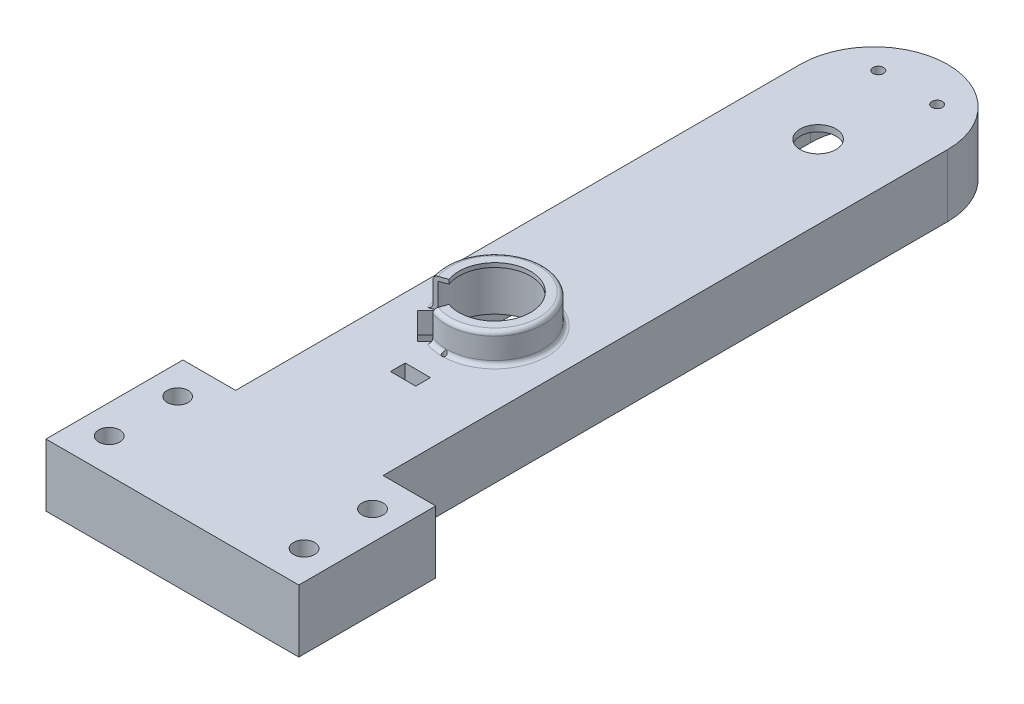
SolidWorks part; units mm, degrees
ref_plane "Front Plane" through (0, 0, 0) normal (0, 0, 1) x (1, 0, 0)
ref_plane "Top Plane" through (0, 0, 0) normal (0, 1, 0) x (1, 0, 0)
ref_plane "Right Plane" through (0, 0, 0) normal (1, 0, 0) x (0, 0, -1)
sketch "Sketch1" plane through (0, 0, 0) normal (0, 1, 0) x (1, 0, 0)
  line L0 (-5.6852, 33.5) -> (5.6852, 33.5)
  line L1 (0, 0) -> (0, 26.5) construction
  line L2 (0, 26.5) -> (0, 33.5) construction
  line L3 (-5.6852, 33.5) -> (-11.4774, 17.5861)
  line L4 (0, 0) -> (-21, 0) construction
  line L5 (5.6852, 33.5) -> (11.4774, 17.5861)
  line L6 (5.6852, -33.5) -> (11.4774, -17.5861)
  line L7 (-5.6852, -33.5) -> (5.6852, -33.5)
  line L8 (-5.6852, -33.5) -> (-11.4774, -17.5861)
  line L9 (0, 0) -> (0, -243.5) construction
  line L11 (-30, 26.5) -> (-30, -243.5)
  line L12 (-30, -243.5) -> (30, -243.5)
  line L13 (30, 26.5) -> (30, -243.5)
  arc A0 (-11.4774, 17.5861) -> (-11.4774, -17.5861) centre (0, 0) ccw
  circle A1 centre (0, 26.5) radius 3.5
  circle A2 centre (0, -26.5) radius 3.5
  arc A3 (11.4774, -17.5861) -> (11.4774, 17.5861) centre (0, 0) ccw
  arc A5 (30, 26.5) -> (-30, 26.5) centre (0, 26.5) ccw
  point P1 (0, 56.5)
  dimension "D1" = 11.3704
  dimension "D2" = 42
  dimension "D4" = 7
  dimension "D6" = 7
  dimension "D3" = 33.5
  dimension "D5" = 110
  dimension "D7" = 300
  dimension "D8" = 30
extrude "Boss-Extrude1" add sketch "Sketch1" along normal blind 10 contours L13 A5 L11 L12 A3 L6 L7 L8 A0 L3 L0 L5 region at (0, 0, 107.816)
sketch "Sketch2" plane through (0, 10, 0) normal (0, 1, 0) x (1, 0, 0)
  line L0 (5.6852, 33.5) -> (11.4774, 17.5861) construction
  line L1 (5.6852, -33.5) -> (11.4774, -17.5861) construction
  line L2 (-5.6852, -33.5) -> (5.6852, -33.5) construction
  line L3 (-5.6852, -33.5) -> (-11.4774, -17.5861) construction
  line L4 (-5.6852, 33.5) -> (-11.4774, 17.5861) construction
  line L5 (-5.6852, 33.5) -> (5.6852, 33.5) construction
  line L6 (5.6852, 33.5) -> (11.4774, 17.5861)
  line L7 (5.6852, -33.5) -> (11.4774, -17.5861)
  line L8 (-5.6852, -33.5) -> (5.6852, -33.5)
  line L9 (-5.6852, -33.5) -> (-11.4774, -17.5861)
  line L10 (-5.6852, 33.5) -> (-11.4774, 17.5861)
  line L11 (-5.6852, 33.5) -> (5.6852, 33.5)
  line L12 (-21, 0) -> (0, 0) construction
  arc A0 (11.4774, -17.5861) -> (11.4774, 17.5861) centre (0, 0) ccw construction
  arc A1 (-11.4774, 17.5861) -> (-11.4774, -17.5861) centre (0, 0) ccw construction
  arc A2 (11.4774, -17.5861) -> (11.4774, 17.5861) centre (0, 0) ccw
  arc A3 (-11.4774, 17.5861) -> (-11.4774, -17.5861) centre (0, 0) ccw
  circle A4 centre (0, 26.5) radius 3.5
  circle A5 centre (0, -26.5) radius 3.5
  circle A6 centre (0, 0) radius 7.5
  dimension "D2" = 7
  dimension "D1" = 7
extrude "Boss-Extrude2" add sketch "Sketch2" against normal blind 3
sketch "Sketch5" plane through (0, 7, 0) normal (0, -1, 0) x (1, 0, 0)
  line L0 (11.4774, -17.5861) -> (5.6852, -33.5) construction
  line L1 (-5.6852, -33.5) -> (5.6852, -33.5) construction
  line L2 (-5.6852, -33.5) -> (-11.4774, -17.5861) construction
  line L3 (5.6852, 33.5) -> (11.4774, 17.5861) construction
  line L4 (-5.6852, 33.5) -> (5.6852, 33.5) construction
  line L5 (-5.6852, 33.5) -> (-11.4774, 17.5861) construction
  line L6 (11.4774, -17.5861) -> (5.6852, -33.5)
  line L7 (-5.6852, -33.5) -> (5.6852, -33.5)
  line L8 (-5.6852, -33.5) -> (-11.4774, -17.5861)
  line L9 (5.6852, 33.5) -> (11.4774, 17.5861)
  line L10 (-5.6852, 33.5) -> (5.6852, 33.5)
  line L11 (-5.6852, 33.5) -> (-11.4774, 17.5861)
  arc A4 (-11.4774, -17.5861) -> (11.4774, -17.5861) centre (0, 0) ccw
  arc A5 (11.4774, 17.5861) -> (-11.4774, 17.5861) centre (0, 0) ccw
extrude "Boss-Extrude5" add sketch "Sketch5" along normal up to surface (7 mm away) and the other way through all up to face at (0, 0, 0)
sketch "Sketch6" plane through (0, 7, 0) normal (0, -1, 0) x (1, 0, 0)
  circle A0 centre (0, 0) radius 8.5
extrude "Cut-Extrude1" cut sketch "Sketch6" against normal through all
sketch "Sketch7" plane through (0, 0, 0) normal (0, -1, 0) x (1, 0, 0)
  line L0 (0, 243.5) -> (0, 153.5) construction
  line L1 (-30, 243.5) -> (30, 243.5) construction
  line L4 (-12.0022, 178.2301) -> (-24.7301, 165.5022)
  line L6 (0, 153.5) -> (-23.8437, 177.3437) construction
  line L7 (-24.7301, 165.5022) -> (-19.7804, 160.5524)
  line L8 (-12.0022, 178.2301) -> (-7.0524, 173.2804)
  line L9 (-19.7804, 160.5524) -> (-7.0524, 173.2804) construction
  line L10 (0, 153.5) -> (-30, 153.5) construction
  line L11 (-30, -26.5) -> (-30, 243.5) construction
  arc A0 (-19.7804, 160.5524) -> (-7.0524, 173.2804) centre (0, 153.5) ccw
  circle A1 centre (0, 129.5) radius 1
  circle A2 centre (0, 177.5) radius 1
  dimension "D2" = 42
  dimension "D6" = 24
  dimension "D1" = 90
  dimension "D3" = 45
  dimension "D4" = 18
  dimension "D5" = 7
extrude "Cut-Extrude2" cut sketch "Sketch7" against normal through all
sketch "Sketch9" plane through (0, 0, 0) normal (0, -1, 0) x (1, 0, 0)
  line L0 (-21.6642, 161.2241) -> (-19.7804, 160.5524)
  line L1 (-7.7241, 175.1642) -> (-7.0524, 173.2804)
  arc A0 (-19.7804, 160.5524) -> (-7.0524, 173.2804) centre (0, 153.5) ccw construction
  arc A1 (-19.7804, 160.5524) -> (-7.0524, 173.2804) centre (0, 153.5) ccw
  arc A2 (-21.6642, 161.2241) -> (-7.7241, 175.1642) centre (0, 153.5) ccw
  dimension "D1" = 2
extrude "Boss-Extrude6" add sketch "Sketch9" against normal blind 22
sketch "Sketch10" plane through (0, 22, 0) normal (0, 1, 0) x (1, 0, 0)
  line L0 (-21.6642, -161.2241) -> (-16.0127, -159.2091)
  line L1 (-7.7241, -175.1642) -> (-5.7091, -169.5127)
  arc A0 (-5.7091, -169.5127) -> (-16.0127, -159.2091) centre (0, -153.5) ccw
  arc A3 (-7.7241, -175.1642) -> (-21.6642, -161.2241) centre (0, -153.5) ccw
  circle A5 centre (0, -153.5) radius 23 construction
  circle A7 centre (0, -153.5) radius 17 construction
  point P1 (16, -153.5)
  point P8 (21.0387, -147.0678)
  dimension "D1" = 6
extrude "Boss-Extrude7" add sketch "Sketch10" along normal blind 2
fillet "Fillet1" radius 2 1 edges at (16.2635, 24, 137.2365)
fillet "Fillet3" radius 2 3 edges at (-3.9194, 10, 176.1636) (-18.797, 10, 140.2458) (23, 10, 153.5)
sketch "Sketch11" plane through (0, 0, 0) normal (0, -1, 0) x (1, 0, 0)
  line L0 (0, 153.5) -> (0, 193.5) construction
  line L2 (-6, 197) -> (6, 197)
  line L3 (-6, 197) -> (-6, 190)
  line L4 (-6, 190) -> (6, 190)
  line L5 (6, 197) -> (6, 190)
  line L6 (-6, 197) -> (6, 190) construction
  line L7 (-6, 190) -> (6, 197) construction
  dimension "D1" = 40
  dimension "D2" = 12
  dimension "D3" = 7
extrude "Cut-Extrude3" cut sketch "Sketch11" against normal through all
sketch "Sketch12" plane through (0, 0, 0) normal (0, -1, 0) x (1, 0, 0)
  line L4 (30, -26.5) -> (30, 243.5) construction
  line L5 (-30, -26.5) -> (-30, 243.5) construction
  line L6 (35, 243.5) -> (35, -26.5)
  line L7 (-35, -26.5) -> (-35, 243.5)
  line L8 (35, 243.5) -> (35, -26.5)
  line L9 (-35, -26.5) -> (-35, 243.5)
  line L10 (30, -26.5) -> (30, 243.5)
  line L11 (-30, -26.5) -> (-30, 243.5)
  line L12 (-35, 243.5) -> (-30, 243.5)
  line L13 (30, 243.5) -> (35, 243.5)
  line L14 (-27.9106, -37.5) -> (27.9106, -37.5)
  line L15 (-21, 0) -> (21, 0) construction
  arc A2 (-30, -26.5) -> (30, -26.5) centre (0, -26.5) ccw construction
  arc A3 (-35, -26.5) -> (35, -26.5) centre (0, -26.5) ccw
  arc A4 (-35, -26.5) -> (35, -26.5) centre (0, -26.5) ccw
  arc A5 (-30, -26.5) -> (-27.9106, -37.5) centre (0, -26.5) ccw
  circle A6 centre (0, 0) radius 21 construction
  circle A7 centre (0, 0) radius 21 construction
  arc A8 (27.9106, -37.5) -> (30, -26.5) centre (0, -26.5) ccw
  dimension "D1" = 5
extrude "Boss-Extrude8" add sketch "Sketch12" against normal up to surface (10 mm away) and the other way blind 19.65 up to face at (0, 10, 193.5)
sketch "Sketch13" plane through (0, -19.65, 0) normal (0, -1, 0) x (1, 0, 0)
  line L0 (-27.9106, -37.5) -> (-27.9106, -47.6187) construction
  line L1 (-27.9106, -47.6187) -> (27.9106, -47.6187) construction
  line L2 (27.9106, -47.6187) -> (27.9106, -37.5) construction
  line L3 (-27.9106, -42.5594) -> (0, -42.5594) construction
  line L4 (0, -42.5594) -> (0, -37.5) construction
  line L5 (27.9106, -37.5) -> (-27.9106, -37.5) construction
  arc A0 (-35, -26.5) -> (35, -26.5) centre (0, -26.5) ccw construction
  circle A1 centre (-13.9553, -42.5594) radius 2.5
  circle A2 centre (13.9553, -42.5594) radius 2.5
extrude "Cut-Extrude4" cut sketch "Sketch13" against normal through all
sketch "Sketch14" plane through (0, 10, 0) normal (0, 1, 0) x (1, 0, 0)
  line L1 (0, -153.5) -> (0, -274) construction
  line L2 (-35, -243.5) -> (35, -243.5) construction
  line L3 (-60, -306.5) -> (60, -306.5)
  line L9 (-60, -306.5) -> (-60, -241.5)
  line L10 (-60, -241.5) -> (60, -241.5)
  line L11 (60, -306.5) -> (60, -241.5)
  line L12 (-60, -306.5) -> (60, -241.5) construction
  line L13 (-60, -241.5) -> (60, -306.5) construction
  line L14 (32.5, -290.25) -> (60, -290.25) construction
  line L15 (32.5, -274) -> (60, -274) construction
  line L16 (32.5, -274) -> (32.5, -306.5) construction
  circle A1 centre (46.25, -290.25) radius 5
  circle A2 centre (-46.25, -290.25) radius 5
  circle A3 centre (46.25, -257.75) radius 5
  circle A4 centre (-46.25, -257.75) radius 5
  dimension "D1" = 65
  dimension "D3" = 2
  dimension "D2" = 120
extrude "Boss-Extrude9" add sketch "Sketch14" against normal up to surface (29.65 mm away) up to face at (-13.9553, -19.65, -45.0594)
sketch "Sketch15" plane through (0, -19.65, 0) normal (0, -1, 0) x (1, 0, 0)
  line L0 (-60, 274) -> (60, 274) construction
  line L1 (-60, 241.5) -> (-60, 306.5) construction
  line L2 (60, 306.5) -> (60, 241.5) construction
  line L3 (-30, 296.5) -> (30, 296.5)
  line L5 (-30, 296.5) -> (-30, 241.5)
  line L6 (-30, 241.5) -> (30, 241.5)
  line L7 (30, 296.5) -> (30, 241.5)
  line L8 (-30, 306.5) -> (30, 241.5) construction
  line L9 (-30, 241.5) -> (30, 306.5) construction
  point P6 (0, 274)
extrude "Cut-Extrude5" cut sketch "Sketch15" against normal up to surface (19.65 mm away) up to face at (0, 0, 21)
